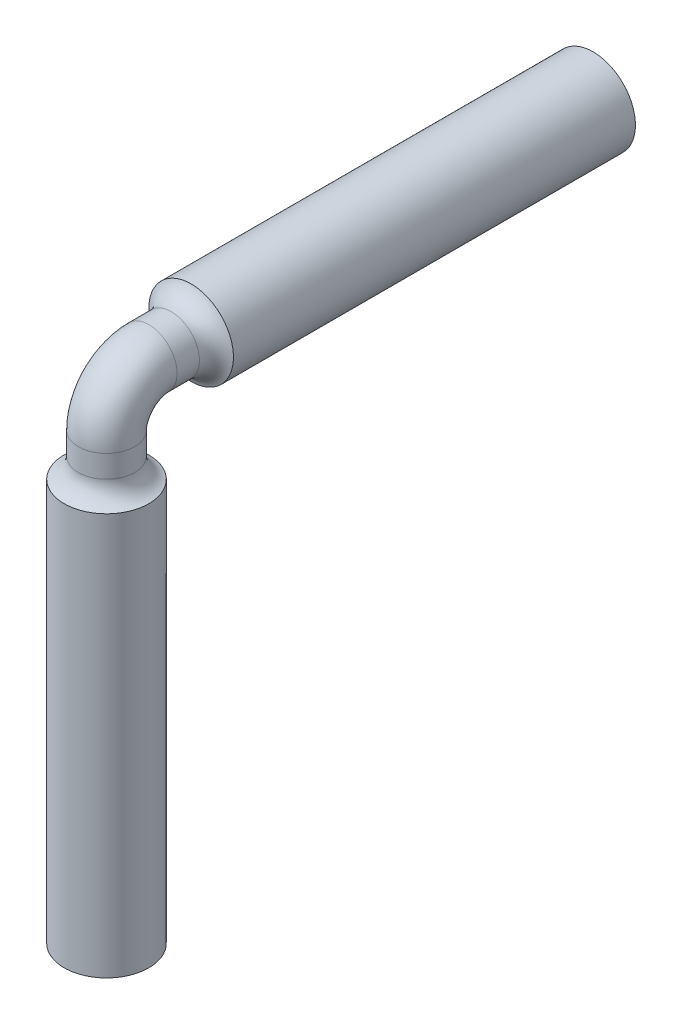
SolidWorks part; units mm, degrees
ref_plane "정면" through (0, 0, 0) normal (0, 0, 1) x (1, 0, 0)
ref_plane "윗면" through (0, 0, 0) normal (0, 1, 0) x (1, 0, 0)
ref_plane "우측면" through (0, 0, 0) normal (1, 0, 0) x (0, 0, -1)
sketch "스케치1" plane through (0, 0, 0) normal (0, 1, 0) x (1, 0, 0)
  circle A0 centre (0, 0) radius 2
  dimension "D1" = 4
sketch "스케치2" plane through (0, 0, 0) normal (1, 0, 0) x (0, 0, -1)
  line L0 (0, 0) -> (0, 31.5)
  line L1 (2, 0) -> (-2, 0) construction
  line L2 (3, 34.5) -> (34.5, 34.5)
  arc A0 (0, 31.5) -> (3, 34.5) centre (3, 31.5) cw
  point P7 (0, 34.5)
  dimension "D3" = 3
  dimension "D1" = 34.5
  dimension "D2" = 34.5
sweep "스윕1" add profiles "스케치1" path "스케치2"
sketch "스케치3" plane through (0, 0, 0) normal (0, -1, 0) x (1, 0, 0)
  circle A0 centre (0, 0) radius 3
  dimension "D1" = 6
extrude "보스-돌출1" add sketch "스케치3" against normal blind 28.5
sketch "스케치4" plane through (0, 0, -34.5) normal (0, 0, -1) x (-1, 0, 0)
  circle A0 centre (0, 34.5) radius 3
  dimension "D1" = 6
extrude "보스-돌출2" add sketch "스케치4" against normal blind 28.5
fillet "필렛1" radius 1.5 2 edges at (0, 28.5, -2) (-2, 34.5, -6)
